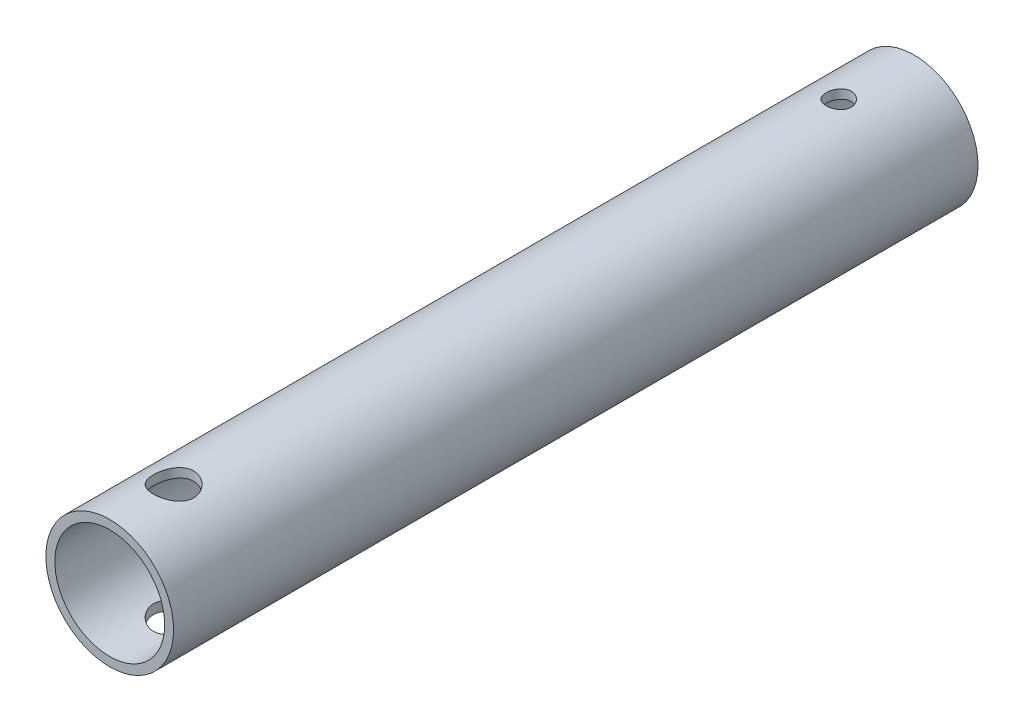
SolidWorks part; units mm, degrees
material "1060 Alloy"
ref_plane "Front" through (0, 0, 0) normal (0, 0, 1) x (1, 0, 0)
ref_plane "Top" through (0, 0, 0) normal (0, 1, 0) x (1, 0, 0)
ref_plane "Right" through (0, 0, 0) normal (1, 0, 0) x (0, 0, -1)
sketch "Sketch1" plane through (0, 0, 0) normal (0, 0, 1) x (1, 0, 0)
  circle A0 centre (0, 0) radius 6.35
  circle A1 centre (0, 0) radius 5.461
extrude "Extrude1" add sketch "Sketch1" along normal blind 80
sketch "Sketch2" plane through (0, 0, 0) normal (0, 1, 0) x (1, 0, 0)
  line L0 (0, 0) -> (0, -7.5)
  line L2 (-6.35, -80) -> (6.35, -80) construction
  line L3 (0, -80) -> (0, -73.65)
  circle A0 centre (0, -7.5) radius 1.25
  circle A1 centre (0, -73.65) radius 2
  dimension "D1" = 4
  dimension "D2" = 2.5
  dimension "D3" = 7.5
  dimension "D4" = 6.35
extrude "Cut-Extrude1" cut sketch "Sketch2" against normal blind 38.1 and the other way blind 38.1
